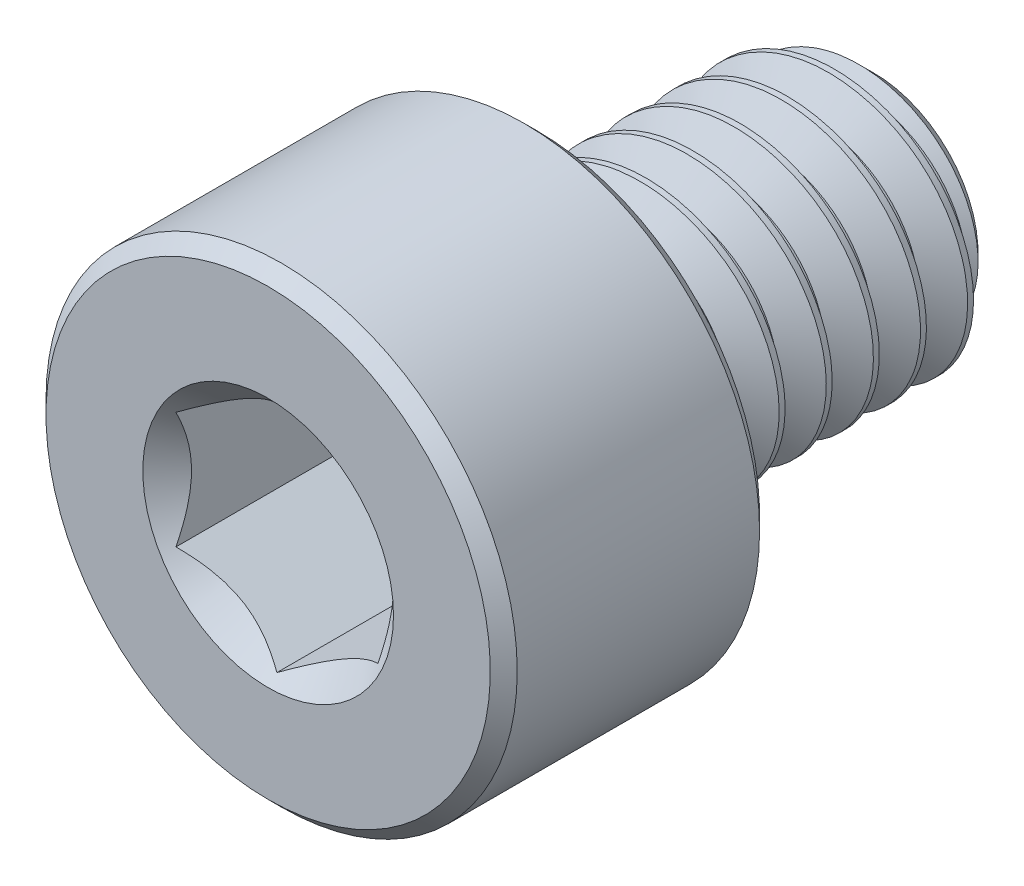
SolidWorks part; units mm, degrees
ref_plane "Front Plane" through (0, 0, 0) normal (0, 0, 1) x (1, 0, 0)
ref_plane "Top Plane" through (0, 0, 0) normal (0, 1, 0) x (1, 0, 0)
ref_plane "Right Plane" through (0, 0, 0) normal (1, 0, 0) x (0, 0, -1)
sketch "Sketch1" plane through (0, 0, 0) normal (1, 0, 0) x (0, 0, -1)
  line L0 (-4.5, 0) -> (4.5, 0) construction
  line L1 (4.5, 0) -> (4.5, 1.5453) construction
  line L2 (4.5, 1.5453) -> (4.0453, 2) construction
  line L3 (4.0453, 2) -> (3.975, 2) construction
  line L4 (3.975, 2) -> (-0.5, 2) construction
  line L5 (-0.5, 2) -> (-0.5, 3.5) construction
  line L6 (-0.5, 3.5) -> (-4.5, 3.5) construction
  line L7 (-4.5, 3.5) -> (-4.5, 0) construction
  line L8 (4.5, 1.5453) -> (4.5, 2) construction
  line L9 (4.4563, 2.0758) -> (4.8063, 1.4696) construction
  line L10 (4.8063, 1.4696) -> (5.1562, 2.0758) construction
  line L11 (5.1562, 2.0758) -> (4.4563, 2.0758) construction
  line L12 (4.8063, 2.0758) -> (4.8063, 2) construction
  line L13 (4.8063, 1.4696) -> (4.8063, 1.5453) construction
  line L14 (4.7625, 1.5453) -> (4.85, 1.5453) construction
  line L15 (4.5, 2) -> (5.1125, 2) construction
  line L16 (4.4781, 2.0379) -> (5.1344, 2.0379) construction
  line L17 (4.5, 0) -> (4.5, -2) construction
  line L18 (-0.7, 3.5) -> (-0.5, 3.3) construction
  line L19 (-4.3, 3.5) -> (-4.5, 3.3) construction
  line L20 (-0.5, 2) -> (-0.5, 0) construction
  line L21 (-0.5, 1) -> (1.1667, 1) construction
  line L22 (1.1667, 1) -> (2.8333, 1) construction
  line L23 (2.8333, 1) -> (4.5, 1) construction
  line L24 (1.1667, 1) -> (1.1667, 2) construction
  line L25 (1.1667, 2) -> (1.1667, 3.5) construction
  line L26 (2.8333, 1) -> (2.8333, 3.5) construction
  point P0 (-4.5, 1.5)
  point P3 (2.75, 2)
  point P4 (0, 0)
  point P18 (2.8333, 2)
  point P22 (4.8063, 1.5453)
  point P24 (3.975, 2)
  point P25 (4.8063, 2)
  point P28 (4.8063, 2.0379)
  point P29 (2.75, -2)
  point P30 (1.1667, 2)
  point P31 (-2.5, 3.5)
  point P37 (-1.2, 3.5)
  point P38 (-4.2, 3.5)
  point P45 (1.1667, 1)
  point P46 (2.8333, 1)
  dimension "D2" = 0.0875
  dimension "D7" = 0.2
  dimension "D8" = 0.2
  dimension "D9" = 0.2
  dimension "D10" = 0.1
  dimension "D11" = 0.5
  dimension "Drive Size" = 3
  dimension "Head Diameter" = 7
  dimension "Head Height" = 4
  dimension "Thread Pitch" = 0.7
  dimension "Thread Dia" = 4
  dimension "Length" = 5
  dimension "D12" = 0.525
  dimension "D4" = 1.75
  dimension "D3" = 45
sketch "Sketch2" plane through (0, 0, 0) normal (1, 0, 0) x (0, 0, -1)
  line L0 (-4.5, 0) -> (-4.5, 3.3)
  line L1 (-4.3, 3.5) -> (-0.7, 3.5)
  line L2 (-0.5, 3.3) -> (-0.5, 2.2)
  line L4 (4.0453, 2) -> (4.5, 1.5453)
  line L5 (4.5, 1.5453) -> (4.5, 0)
  line L6 (-0.5, 3.5) -> (-4.5, 3.5) construction
  line L7 (4.5, 0) -> (-4.5, 0)
  line L8 (-4.3, 3.5) -> (-4.5, 3.3) construction
  line L10 (-4.3, 3.5) -> (-4.5, 3.3)
  line L14 (-0.7, 3.5) -> (-0.5, 3.3) construction
  line L16 (-0.7, 3.5) -> (-0.5, 3.3)
  line L17 (-0.5, 2) -> (-0.5, 3.5) construction
  line L19 (-0.3, 2) -> (4.0453, 2)
  line L20 (3.975, 2) -> (-0.5, 2) construction
  arc A1 (-0.5, 2.2) -> (-0.3, 2) centre (-0.3, 2.2) ccw
  dimension "D3" = 0.2
revolve "Revolve1" add sketch "Sketch2" angle 360 about L7
sketch "Sketch3" plane through (0, 0, 4.5) normal (0, 0, 1) x (1, 0, 0)
  line L1 (1.5, -0.866) -> (1.5, 0.866)
  line L2 (1.5, 0.866) -> (0, 1.7321)
  line L3 (0, 1.7321) -> (-1.5, 0.866)
  line L4 (-1.5, 0.866) -> (-1.5, -0.866)
  line L5 (-1.5, -0.866) -> (0, -1.7321)
  line L6 (0, -1.7321) -> (1.5, -0.866)
  circle A0 centre (0, 0) radius 1.5 construction
  circle A1 centre (0, 0) radius 3.5 construction
  circle A2 centre (0, 0) radius 3.5 construction
  circle A3 centre (0, 0) radius 1.7321 construction
  point P13 (0, 0)
  dimension "D1" = 3.4641
extrude "Cut-Extrude1" cut sketch "Sketch3" against normal offset from surface (3 mm away) 1 up to face at (0, 3.3, 0.5)
sketch "Sketch4" plane through (0, 0, 4.5) normal (0, 0, 1) x (1, 0, 0)
  circle A0 centre (0, 0) radius 1.862
  dimension "D1" = 3.7239
extrude "Cut-Extrude2" cut sketch "Sketch4" against normal up to vertex (2 mm away) draft 45 up to point (0, 3.5, 2.5)
sketch "Sketch11" plane through (0, 0, 0) normal (1, 0, 0) x (0, 0, -1)
  line L0 (-4.5, 0) -> (4.5, 0) construction
  line L1 (-4.5, 0) -> (4.5, 0) construction
  line L2 (0.4375, 0) -> (0.4375, 2) construction
  line L3 (3.975, 2) -> (-0.5, 2) construction
  line L4 (3.5625, 0) -> (3.5625, 2) construction
  line L6 (4.5, 1.5453) -> (4.5, 2) construction
  point P2 (0.4375, 0)
  point P3 (3.5625, 0)
  dimension "D1" = 0.9375
  dimension "D2" = 0.9375
sketch "Sketch6" plane through (0, 0, -4.5) normal (0, 0, -1) x (-1, 0, 0)
  circle A0 centre (0, 0) radius 2
curve "Helix/Spiral1" pitch 0.7 height 5.7 turns 8.1429
sketch "Sketch10" plane through (0, 0, 0) normal (1, 0, 0) x (0, 0, -1)
  line L0 (-0.3, -3.5) -> (-0.3, 3.5)
  line L5 (-4.5, 0) -> (4.5, 0) construction
  line L6 (-0.3, 2) -> (-0.3, -2) construction
  point P3 (-0.3, 0)
split "Split1" trim tools "Sketch10" bodies to split 106 resulting bodies 114 115
sketch "Sketch7" plane through (0, 0, 0) normal (1, 0, 0) x (0, 0, -1)
  line L0 (4.4781, 2.0379) -> (5.1344, 2.0379)
  line L1 (5.1344, 2.0379) -> (4.85, 1.5453)
  line L2 (4.85, 1.5453) -> (4.7625, 1.5453)
  line L3 (4.7625, 1.5453) -> (4.4781, 2.0379)
sweep "Cut-Sweep1" cut profiles "Sketch7" path "Helix/Spiral1" align with end faces yes
sketch "Sketch8" plane through (0, 0, 0) normal (1, 0, 0) x (0, 0, -1)
  line L0 (-0.5, 0) -> (-0.5, 2)
  line L1 (-0.3, -2) -> (-0.3, 2) construction
  line L2 (-0.5, 2) -> (-0.3, 2)
  line L4 (-0.3, 2) -> (0.8547, 0)
  line L5 (0.8547, 0) -> (-0.5, 0)
  line L6 (3.975, 2) -> (-0.5, 2) construction
  line L7 (-4.5, 0) -> (4.5, 0) construction
  dimension "D1" = 60
revolve "Revolve2" add sketch "Sketch8" angle 360 about L5
equation "\"D2@Sketch1\" = \"Thread Pitch@Sketch1\" / 8"
equation "\"D4@Helix/Spiral1\" = \"Thread Pitch@Sketch1\""
equation "\"D7@Sketch1\" = \"Head Height@Sketch1\" * .05"
equation "\"D8@Sketch1\"=\"D7@Sketch1\""
equation "\"D9@Sketch1\"=\"D7@Sketch1\""
equation "\"D10@Sketch1\"=\"D7@Sketch1\"/2"
equation "\"D11@Sketch1\"=\"D10@Sketch1\"*5"
equation "\"D4@Sketch1\"=\"Thread Pitch@Sketch1\"*2.5"
equation "\"D12@Sketch1\"=\"Thread Pitch@Sketch1\"*.75"
equation "\"D3@Helix/Spiral1\"=\"Length@Sketch1\"+\"Thread Pitch@Sketch1\""
equation "\"D3@Sketch2\"=\"Thread Dia@Sketch1\"*0.05"
equation "\"D1@Sketch11\"=\"Length@Sketch1\"*0.1875"
equation "\"D2@Sketch11\"=\"D1@Sketch11\""
equation "\"D1@Sketch4\"=\"D1@Sketch3\"*1.075"
